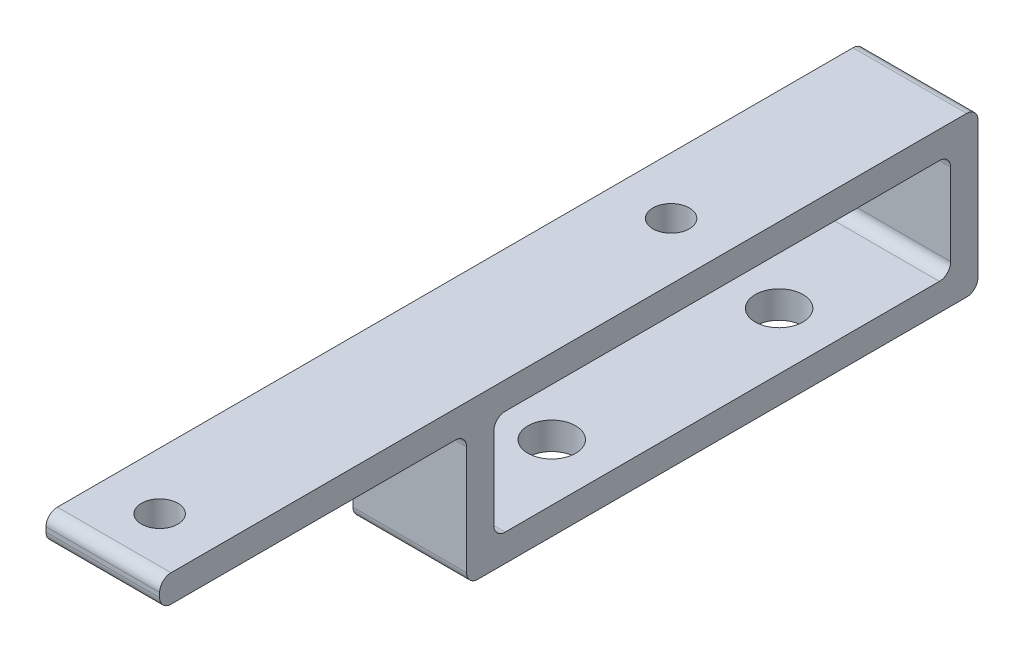
SolidWorks part; units mm, degrees
ref_plane "Front Plane" through (0, 0, 0) normal (0, 0, 1) x (1, 0, 0)
ref_plane "Top Plane" through (0, 0, 0) normal (0, 1, 0) x (1, 0, 0)
ref_plane "Right Plane" through (0, 0, 0) normal (1, 0, 0) x (0, 0, -1)
sketch "Sketch1" plane through (0, 0, 0) normal (1, 0, 0) x (0, 0, -1)
  line L0 (0, 11.6) -> (0, 0)
  line L1 (0, 14) -> (45, 14)
  line L2 (0, 14) -> (-27, 14)
  line L3 (-27, 14) -> (-27, 11.6)
  line L4 (45, 0) -> (0, 0)
  line L5 (45, 14) -> (45, 0)
  line L6 (-27, 11.6) -> (0, 11.6)
  dimension "D1" = 14
  dimension "D2" = 45
  dimension "D3" = 45
  dimension "D4" = 2.4
  dimension "D5" = 72
extrude "Boss-Extrude1" add sketch "Sketch1" along normal blind 10
sketch "Sketch3" plane through (0, 0, 0) normal (0, 1, 0) x (1, 0, 0)
  line L0 (0, 22.5) -> (10, 22.5) construction
  line L4 (10, 0) -> (10, 45) construction
  line L8 (5, 12.5) -> (5, 32.5) construction
  line L9 (0, 0) -> (0, 45) construction
  circle A0 centre (5, 32.5) radius 2.1
  circle A1 centre (5, 12.5) radius 2.1
  point P5 (10, 22.5)
  point P18 (5, 22.5)
  point P19 (0, 22.5)
  dimension "D1" = 4.2
  dimension "D3" = 20
sketch "Sketch4" plane through (10, 0, 0) normal (1, 0, 0) x (0, 0, -1)
  line L8 (2.4, 11.6) -> (42.6, 11.6)
  line L12 (2.4, 2.4) -> (42.6, 2.4)
  line L13 (42.6, 2.4) -> (42.6, 11.6)
  line L14 (2.4, 11.6) -> (2.4, 2.4)
  line L15 (42.6, 11.6) -> (2.4, 11.6)
  line L16 (2.4, 2.4) -> (42.6, 2.4)
  line L17 (42.6, 2.4) -> (42.6, 11.6)
  line L18 (2.4, 11.6) -> (2.4, 2.4)
  dimension "D1" = 2.4
extrude "Cut-Extrude1" cut sketch "Sketch4" against normal through all
extrude "Cut-Extrude2" cut sketch "Sketch3" along normal up to surface (2.4 mm away) up to face at (5, 2.4, -22.5)
sketch "Sketch5" plane through (0, 14, 0) normal (0, 1, 0) x (1, 0, 0)
  line L0 (10, -27) -> (0, -27) construction
  line L3 (5, 23) -> (5, -22) construction
  line L4 (0, 0.5) -> (10, 0.5) construction
  line L5 (0, 45) -> (0, -27) construction
  line L6 (10, 45) -> (10, -27) construction
  circle A0 centre (5, 23) radius 1.6
  circle A1 centre (5, -22) radius 1.6
  point P9 (5, 0.5)
  point P15 (5, 0.5)
  dimension "D1" = 3.2
  dimension "D2" = 45
  dimension "D3" = 5
extrude "Cut-Extrude3" cut sketch "Sketch5" against normal up to surface (2.4 mm away) up to face at (5, 11.6, -22.5)
fillet "Fillet1" radius 1 10 edges at (5, 11.6, 0) (5, 11.6, -42.6) (5, 2.4, -42.6) (5, 14, 27) (5, 11.6, -2.4) (5, 2.4, -2.4) (5, 14, -45) (5, 0, -45) (5, 0, 0) (5, 11.6, 27)
